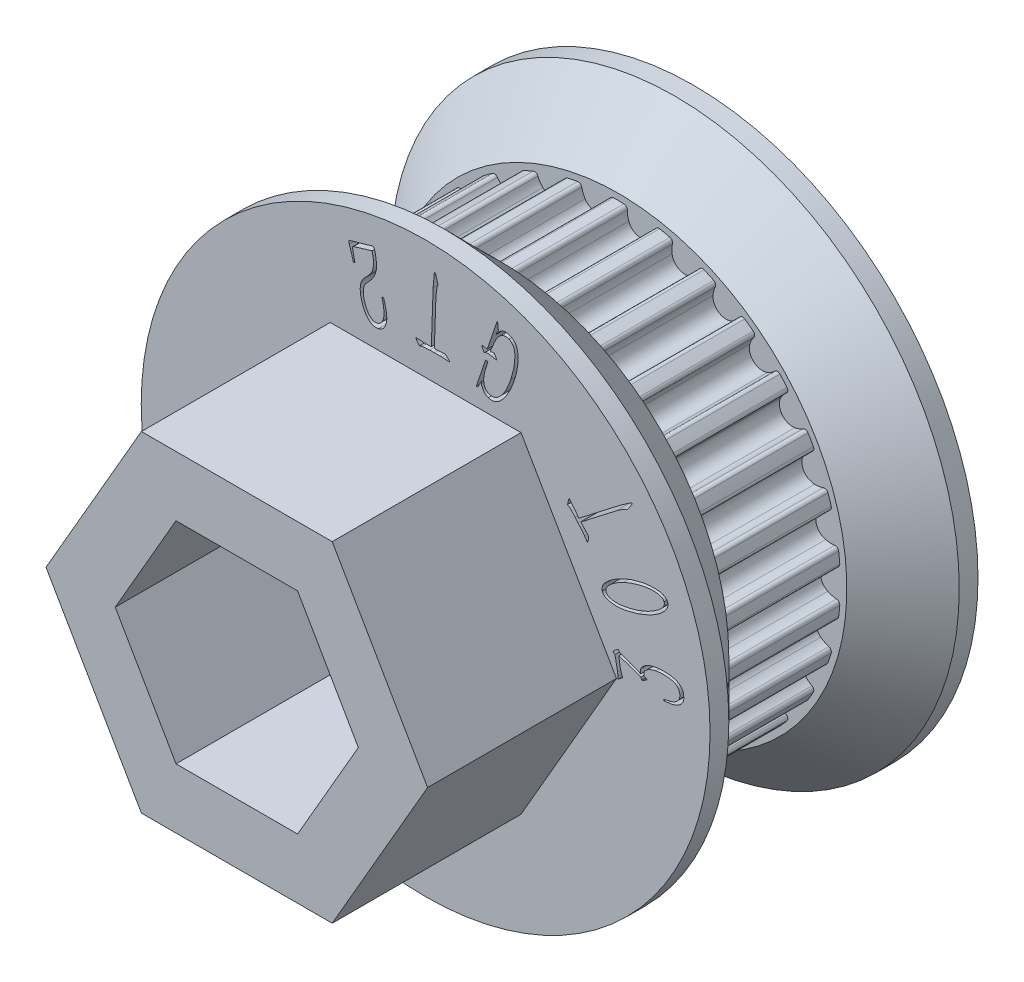
SolidWorks part; units mm, degrees
ref_plane "Front" through (0, 0, 0) normal (0, 0, 1) x (1, 0, 0)
ref_plane "Top" through (0, 0, 0) normal (0, 1, 0) x (1, 0, 0)
ref_plane "Right" through (0, 0, 0) normal (1, 0, 0) x (0, 0, -1)
ref_axis "CENTRAL AXIS" through (0, 0, 0) along (0, 0, 1)
sketch "Sketch1" plane through (0, 0, 0) normal (0, 0, 1) x (1, 0, 0)
  circle A0 centre (0, 0) radius 9.5493
  dimension "D1" = 19.0986
extrude "BASE" add sketch "Sketch1" along normal mid plane 5
sketch "Sketch2" plane through (0, 0, 2.5) normal (0, 0, 1) x (1, 0, 0)
  line L0 (0, 0) -> (0, 9.5493) construction
  line L1 (0.9982, 9.497) -> (0, 0) construction
  line L2 (1.395, 9.4469) -> (1.3698, 9.2068) construction
  line L3 (0, 9.3993) -> (0, 9.5493)
  line L4 (1.9542, 9.1939) -> (1.9854, 9.3406)
  circle A0 centre (0, 0) radius 9.5493 construction
  arc A1 (0, 9.3993) -> (0.224, 9.3966) centre (0, 0) cw
  arc A2 (0.224, 9.3966) -> (0.3704, 9.2415) centre (0.2205, 9.2467) cw
  arc A3 (0.3704, 9.2415) -> (0.4302, 8.8644) centre (1.3698, 9.2068) ccw
  arc A4 (0.4302, 8.8644) -> (1.4222, 8.7601) centre (0.9517, 9.0544) ccw
  arc A5 (0.9982, 9.497) -> (1.395, 9.4469) centre (0, 0) cw construction
  arc A6 (0, 9.5493) -> (1.9854, 9.3406) centre (0, 0) cw
  arc A7 (1.5591, 9.1165) -> (1.4222, 8.7601) centre (0.5744, 9.2904) cw
  arc A8 (1.7345, 9.2379) -> (1.5591, 9.1165) centre (1.7069, 9.0904) ccw
  arc A9 (1.9542, 9.1939) -> (1.7345, 9.2379) centre (0, 0) ccw
  dimension "D3" = 0.15
  dimension "D4" = 1
  dimension "D6" = 0.555
  dimension "D1" = 0.15
  dimension "D5" = 6
  dimension "D7" = 1
  dimension "D2" = 0.4
extrude "TOOTH PROFILE" cut sketch "Sketch2" against normal through all
pattern_circular "TEETH PATTERN" count 30 over 360 about axis through (0, 0, 2.5) along (0, 0, 1) of "TOOTH PROFILE"
sketch "Sketch3" plane through (0, 0, 2.5) normal (0, 0, 1) x (1, 0, 0)
  circle A0 centre (0, 0) radius 12.0493
  dimension "D1" = 24.0986
extrude "FLANGE" add sketch "Sketch3" along normal blind 3.175
mirror "FLANGE MIRROR" about plane through (0, 0, 0) normal (0, 0, 1) of "FLANGE"
chamfer "FLANGE CHAMFER" distance 2.3813 angle 45 2 edges at (12.0493, 0, -2.5) (12.0493, 0, 2.5)
sketch "Sketch4" [suppressed] plane through (0, 0, 7.675) normal (0, 0, 1) x (1, 0, 0)
  line L1 (2.823, -4.8895) -> (5.6459, 0)
  line L2 (5.6459, 0) -> (2.823, 4.8895)
  line L3 (2.823, 4.8895) -> (-2.823, 4.8895)
  line L4 (-2.823, 4.8895) -> (-5.6459, 0)
  line L5 (-5.6459, 0) -> (-2.823, -4.8895)
  line L6 (-2.823, -4.8895) -> (2.823, -4.8895)
  circle A0 centre (0, 0) radius 4.8895 construction
  dimension "D1" = 9.779
extrude "0.375 HEX BORE" [suppressed] cut sketch "Sketch4" against normal through all
chamfer "Chamfer2" [suppressed] distance 0.7937 angle 45
sketch "Sketch7" [suppressed] plane through (0, 0, 7.675) normal (0, 0, 1) x (1, 0, 0)
  line L1 (3.7395, -6.477) -> (7.479, 0)
  line L2 (7.479, 0) -> (3.7395, 6.477)
  line L3 (3.7395, 6.477) -> (-3.7395, 6.477)
  line L4 (-3.7395, 6.477) -> (-7.479, 0)
  line L5 (-7.479, 0) -> (-3.7395, -6.477)
  line L6 (-3.7395, -6.477) -> (3.7395, -6.477)
  circle A0 centre (0, 0) radius 6.477 construction
  dimension "D1" = 12.954
extrude "0.5 HEX BORE" [suppressed] cut sketch "Sketch7" against normal through all
chamfer "Chamfer3" [suppressed] distance 0.7937 angle 45
sketch "Sketch8" [suppressed] plane through (0, 0, -7.675) normal (0, 0, -1) x (-1, 0, 0)
  circle A0 centre (0, 0) radius 11.2395
  dimension "D1" = 22.479
extrude "Cut-Extrude6" [suppressed] cut sketch "Sketch8" against normal blind 5.6134
mirror "BEARING BORE MIRROR" [suppressed] about plane through (0, 0, 0) normal (0, 0, 1)
sketch "Sketch9" [suppressed] plane through (0, 0, -2.0616) normal (0, 0, -1) x (-1, 0, 0)
  circle A0 centre (0, 0) radius 7.9375
  dimension "D1" = 15.875
extrude "0.875 THRU HOLE" [suppressed] cut sketch "Sketch9" against normal through all
chamfer "Chamfer4" [suppressed] distance 0.7937 angle 45
sketch "Sketch10" [suppressed] plane through (0, 0, -7.675) normal (0, 0, -1) x (-1, 0, 0)
  circle A0 centre (0, 0) radius 14.4145
  dimension "D1" = 28.829
extrude "BORE" [suppressed] cut sketch "Sketch10" against normal blind 6.35
mirror "BORE MIRROR" [suppressed] about plane through (0, 0, 0) normal (0, 0, 1)
sketch "Sketch11" [suppressed] plane through (0, 0, -1.325) normal (0, 0, -1) x (-1, 0, 0)
  circle A0 centre (0, 0) radius 11.1125
  dimension "D1" = 22.225
extrude "THRU HOLE" [suppressed] cut sketch "Sketch11" against normal through all
chamfer "Chamfer5" [suppressed] distance 0.7937 angle 45
sketch "Sketch5" plane through (0, 0, 5.675) normal (0, 0, 1) x (1, 0, 0)
  circle A0 centre (0, 0) radius 11.2555 construction
  circle A1 centre (0, 0) radius 12.0493 construction
  text T0 "30T GT2" font "@HYSWLongFangSong" height 3.175
  dimension "D1" = 0.7937
extrude "ETCH SIDE 1" cut sketch "Sketch5" against normal blind 1
sketch "Sketch6" plane through (0, 0, -5.675) normal (0, 0, -1) x (-1, 0, 0)
  line L0 (0, 11.2555) -> (0, 0) construction
  circle A0 centre (0, 0) radius 11.2555 construction
  circle A2 centre (0, 0) radius 12.0493 construction
  text T0 "30T GT2" font "@HYSWLongFangSong" height 3.175
  dimension "D1" = 0.7937
extrude "ETCH SIDE 2" cut sketch "Sketch6" against normal blind 1
sketch "Sketch12" plane through (0, 0, -5.675) normal (0, 0, -1) x (-1, 0, 0)
  line L1 (3.5796, -6.2) -> (7.1591, 0)
  line L2 (7.1591, 0) -> (3.5796, 6.2)
  line L3 (3.5796, 6.2) -> (-3.5796, 6.2)
  line L4 (-3.5796, 6.2) -> (-7.1591, 0)
  line L5 (-7.1591, 0) -> (-3.5796, -6.2)
  line L6 (-3.5796, -6.2) -> (3.5796, -6.2)
  circle A0 centre (0, 0) radius 6.2 construction
  dimension "D1" = 12.4
extrude "Cut-Extrude7" cut sketch "Sketch12" against normal blind 10
sketch "Sketch13" plane through (0, 0, 5.675) normal (0, 0, 1) x (1, 0, 0)
  line L19 (5.15, 0) -> (2.575, 4.46)
  line L20 (2.575, 4.46) -> (-2.575, 4.46)
  line L21 (-2.575, 4.46) -> (-5.15, 0)
  line L22 (-5.15, 0) -> (-2.575, -4.46)
  line L23 (-2.575, -4.46) -> (2.575, -4.46)
  line L24 (2.575, -4.46) -> (5.15, 0)
  circle A0 centre (0, 0) radius 4.46 construction
  circle A1 centre (0, 0) radius 5.15 construction
  dimension "D1" = 10.3
extrude "Extrude-Thin1" add sketch "Sketch13" along normal blind 8 thin thin type one direction wall 2.54
equation "\"n\"= 30"
equation "\"p\"= 2mm"
equation "\"pd\"= \"n\" * \"p\" / pi"
equation "\"D1@Sketch1\"=\"pd\""
equation "\"D5@Sketch2\"=180/\"n\""
equation "\"D1@TEETH PATTERN\" = \"n\""
equation "\"w\"= 5mm"
equation "\"D1@BASE\" = \"w\""
equation "\"D1@Sketch3\"=\"pd\"+5mm"
